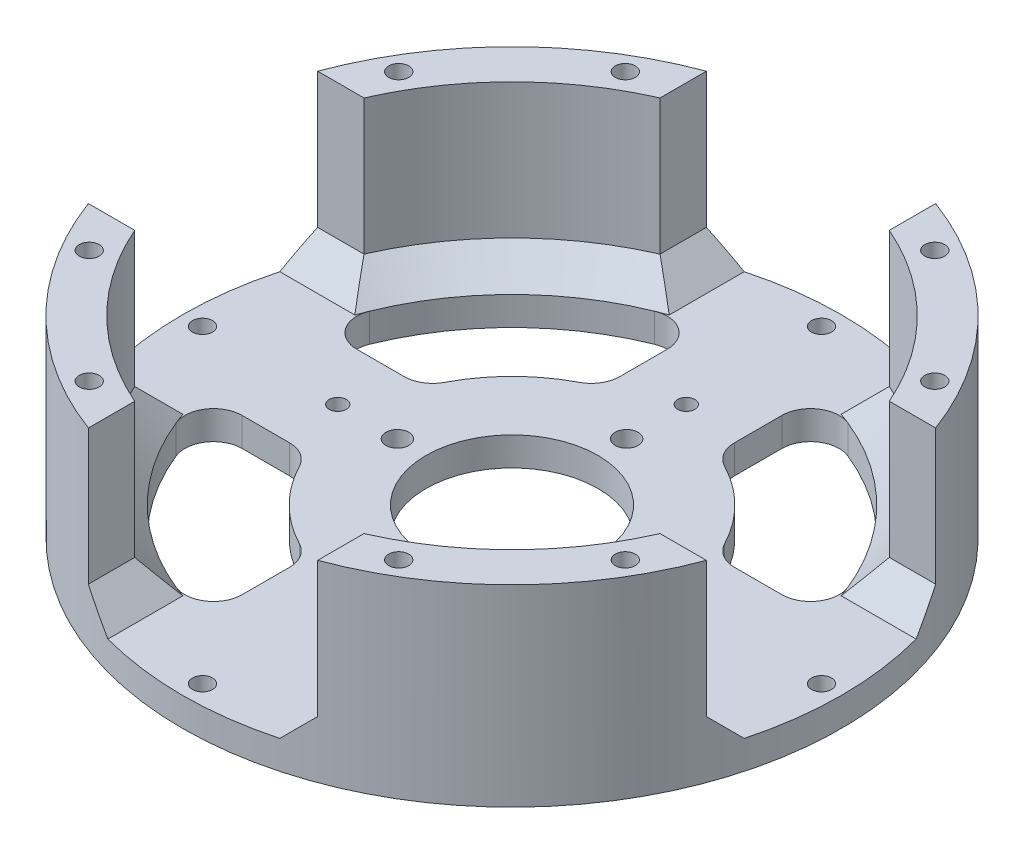
SolidWorks part; units mm, degrees
ref_plane "Front Plane" through (0, 0, 0) normal (0, 0, 1) x (1, 0, 0)
ref_plane "Top Plane" through (0, 0, 0) normal (0, 1, 0) x (1, 0, 0)
ref_plane "Right Plane" through (0, 0, 0) normal (1, 0, 0) x (0, 0, -1)
sketch "Sketch1" plane through (0, 0, 0) normal (0, 1, 0) x (1, 0, 0)
  circle A0 centre (0, 0) radius 57.5
  dimension "D1" = 115
extrude "Boss-Extrude1" add sketch "Sketch1" along normal blind 33.6
sketch "Sketch2" plane through (0, 33.6, 0) normal (0, 1, 0) x (1, 0, 0)
  circle A0 centre (0, 0) radius 50
  dimension "D1" = 100
extrude "Cut-Extrude1" cut sketch "Sketch2" against normal blind 28.6
sketch "Sketch3" plane through (0, 0, 0) normal (0, -1, 0) x (1, 0, 0)
  line L0 (0, 62.4892) -> (0, -59.6631) construction
  line L1 (-72.2237, 0) -> (67.9845, 0) construction
  line L6 (43.8748, 10) -> (43.8748, -10)
  line L7 (43.8748, 10) -> (25.6174, 10)
  line L8 (43.8748, -10) -> (25.6174, -10)
  line L9 (25.6174, 10) -> (25.6174, -10)
  line L10 (-10, -43.8748) -> (10, -43.8748)
  line L11 (-10, -43.8748) -> (-10, -25.6174)
  line L12 (10, -43.8748) -> (10, -25.6174)
  line L13 (-10, -25.6174) -> (10, -25.6174)
  line L14 (-43.8748, 10) -> (-43.8748, -10)
  line L15 (-43.8748, 10) -> (-25.6174, 10)
  line L16 (-43.8748, -10) -> (-25.6174, -10)
  line L17 (-25.6174, 10) -> (-25.6174, -10)
  line L18 (-10, 43.8748) -> (10, 43.8748)
  line L19 (-10, 43.8748) -> (-10, 25.6174)
  line L20 (10, 43.8748) -> (10, 25.6174)
  line L21 (-10, 25.6174) -> (10, 25.6174)
  circle A0 centre (0, 0) radius 20 construction
  circle A1 centre (0, 0) radius 15
  circle A2 centre (0, 20) radius 2
  circle A3 centre (20, 0) radius 2
  circle A4 centre (0, -20) radius 2
  circle A5 centre (-20, 0) radius 2
  circle A6 centre (0, 0) radius 27.5
  circle A7 centre (0, 0) radius 45
  point P15 (0, 0)
  dimension "D1" = 40
  dimension "D2" = 30
  dimension "D3" = 4
  dimension "D5" = 55
  dimension "D6" = 90
  dimension "D7" = 20
  dimension "D4" = 4
extrude "Cut-Extrude2" cut sketch "Sketch3" against normal blind 31.8 contours L19 A7 L15 A6 | L7 A7 L20 A6 | L12 A7 L8 A6 | L16 A7 L11 A6 | A5 | A1 | A2 | A3 | A4
sketch "Sketch4" plane through (0, 0, 0) normal (0, -1, 0) x (1, 0, 0)
  line L1 (30.4056, 0) -> (0, 30.4056) construction
  line L2 (0, 30.4056) -> (-30.4056, 0) construction
  line L3 (-30.4056, 0) -> (0, -30.4056) construction
  line L4 (0, -30.4056) -> (30.4056, 0) construction
  circle A0 centre (0, 0) radius 54 construction
  circle A1 centre (0, 54) radius 1.75
  circle A2 centre (27, 46.7654) radius 1.75
  circle A3 centre (46.7654, 27) radius 1.75
  circle A4 centre (54, 0) radius 1.75
  circle A5 centre (46.7654, -27) radius 1.75
  circle A6 centre (27, -46.7654) radius 1.75
  circle A7 centre (0, -54) radius 1.75
  circle A8 centre (-27, -46.7654) radius 1.75
  circle A9 centre (-46.7654, -27) radius 1.75
  circle A10 centre (-54, 0) radius 1.75
  circle A11 centre (-46.7654, 27) radius 1.75
  circle A12 centre (-27, 46.7654) radius 1.75
  circle A13 centre (0, 0) radius 21.5 construction
  circle A14 centre (0, 30.4056) radius 1.5
  circle A15 centre (30.4056, 0) radius 1.5
  circle A16 centre (0, -30.4056) radius 1.5
  circle A17 centre (-30.4056, 0) radius 1.5
  point P29 (0, 0)
  point P43 (0, 0)
  dimension "D1" = 108
  dimension "D2" = 3.5
  dimension "D5" = 3
  dimension "D4" = 43
  dimension "D3" = 12
  dimension "D6" = 4
extrude "Cut-Extrude3" cut sketch "Sketch4" against normal blind 50
sketch "Sketch6" plane through (0, 0, 0) normal (0, 0, 1) x (1, 0, 0)
  line L0 (0, -2.1266) -> (0, 59.0209)
sketch "Sketch9" plane through (0, 0, 0) normal (0, 0, 1) x (1, 0, 0)
  line L0 (0, -2.1266) -> (0, 59.0209) construction
  line L1 (-20, 33.6) -> (20, 33.6)
  line L2 (-20, 33.6) -> (-20, 5)
  line L3 (-20, 5) -> (20, 5)
  line L4 (20, 33.6) -> (20, 5)
  line L5 (-20, 33.6) -> (20, 5) construction
  line L6 (-20, 5) -> (20, 33.6) construction
  line L7 (50, 33.6) -> (-50, 33.6) construction
  line L8 (-57.5, 0) -> (57.5, 0) construction
  point P0 (0, 19.3)
  dimension "D1" = 5
  dimension "D2" = 40
extrude "Cut-Extrude4" cut sketch "Sketch9" against normal blind 72
pattern_circular "CirPattern1" count 4 over 360 about axis through (0, 0, 0) along (0, 1, 0) of "Cut-Extrude4"
fillet "Fillet2" radius 5 16 edges at (-25.6174, 2.5, 10) (-10, 2.5, 25.6174) (-10, 2.5, 43.8748) (-43.8748, 2.5, 10) (43.8748, 2.5, 10) (25.6174, 2.5, 10) (10, 2.5, 25.6174) (10, 2.5, 43.8748) (10, 2.5, -25.6174) (25.6174, 2.5, -10) (43.8748, 2.5, -10) (10, 2.5, -43.8748) (-25.6174, 2.5, -10) (-10, 2.5, -25.6174) (-10, 2.5, -43.8748) (-43.8748, 2.5, -10)
chamfer "Chamfer1" distance 5 angle 45 12 edges at (-35.3553, 5, -35.3553) (-20, 5, -49.8677) (20, 5, -49.8677) (-35.3553, 5, 35.3553) (35.3553, 5, 35.3553) (35.3553, 5, -35.3553) (-49.8677, 5, 20) (20, 5, 49.8677) (49.8677, 5, -20) (49.8677, 5, 20) (-20, 5, 49.8677) (-49.8677, 5, -20)
